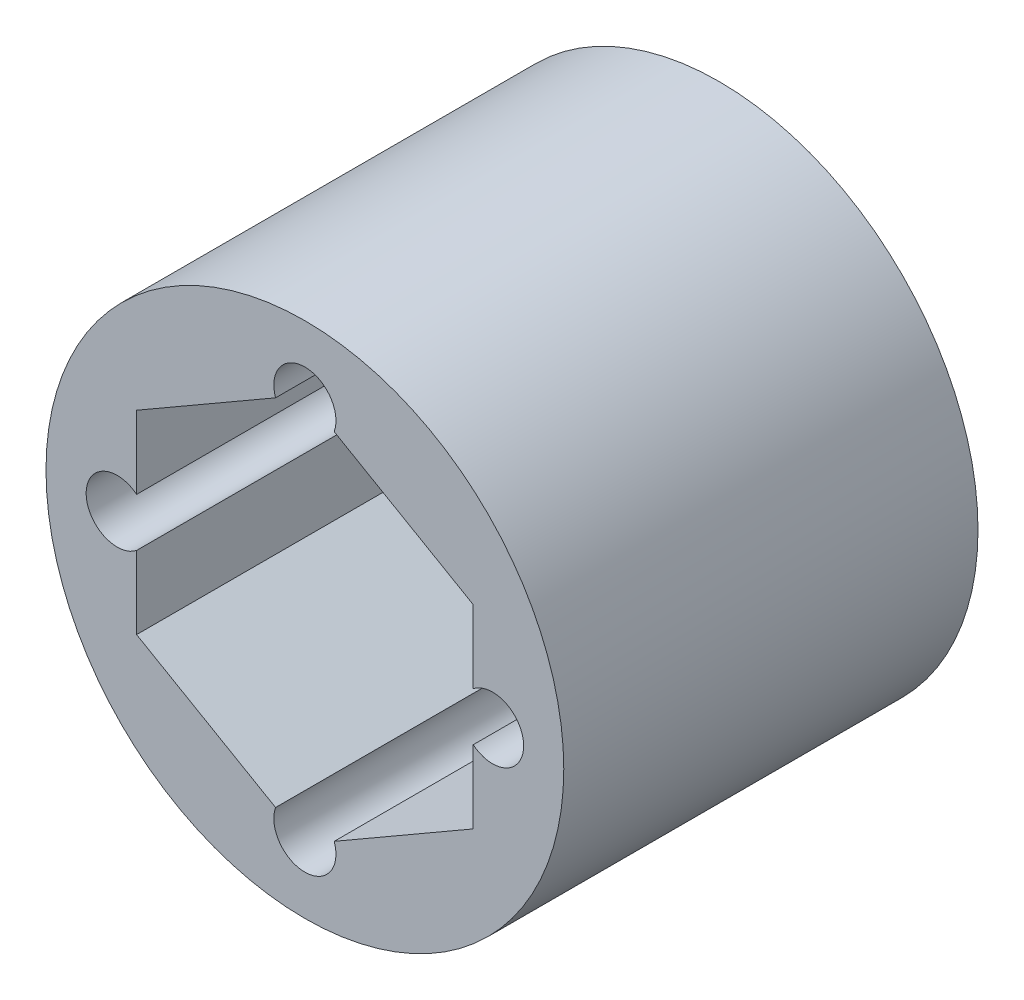
SolidWorks part; units mm, degrees
ref_plane "Front Plane" through (0, 0, 0) normal (0, 0, 1) x (1, 0, 0)
ref_plane "Top Plane" through (0, 0, 0) normal (0, 1, 0) x (1, 0, 0)
ref_plane "Right Plane" through (0, 0, 0) normal (1, 0, 0) x (0, 0, -1)
sketch "Sketch1" plane through (0, 0, 0) normal (0, 0, 1) x (1, 0, 0)
  line L0 (0, 0) -> (0, 12.391) construction
  circle A0 centre (0, 0) radius 10
  circle A1 centre (0, 7.25) radius 1.2
  circle A2 centre (0, 0) radius 4.25
  circle A3 centre (7.25, 0) radius 1.2
  circle A4 centre (0, -7.25) radius 1.2
  circle A5 centre (-7.25, 0) radius 1.2
  dimension "D1" = 20
  dimension "D2" = 2.4
  dimension "D4" = 8.5
  dimension "D3" = 7.25
  dimension "D5" = 4
extrude "Boss-Extrude1" add sketch "Sketch1" along normal blind 16
sketch "Sketch2" plane through (0, 0, 16) normal (0, 0, 1) x (1, 0, 0)
  line L1 (0, 7.5056) -> (-6.5, 3.7528)
  line L2 (-6.5, 3.7528) -> (-6.5, -3.7528)
  line L3 (-6.5, -3.7528) -> (0, -7.5056)
  line L4 (0, -7.5056) -> (6.5, -3.7528)
  line L5 (6.5, -3.7528) -> (6.5, 3.7528)
  line L6 (6.5, 3.7528) -> (0, 7.5056)
  circle A0 centre (0, 0) radius 6.5 construction
  dimension "D1" = 13
extrude "Cut-Extrude1" cut sketch "Sketch2" against normal blind 14
